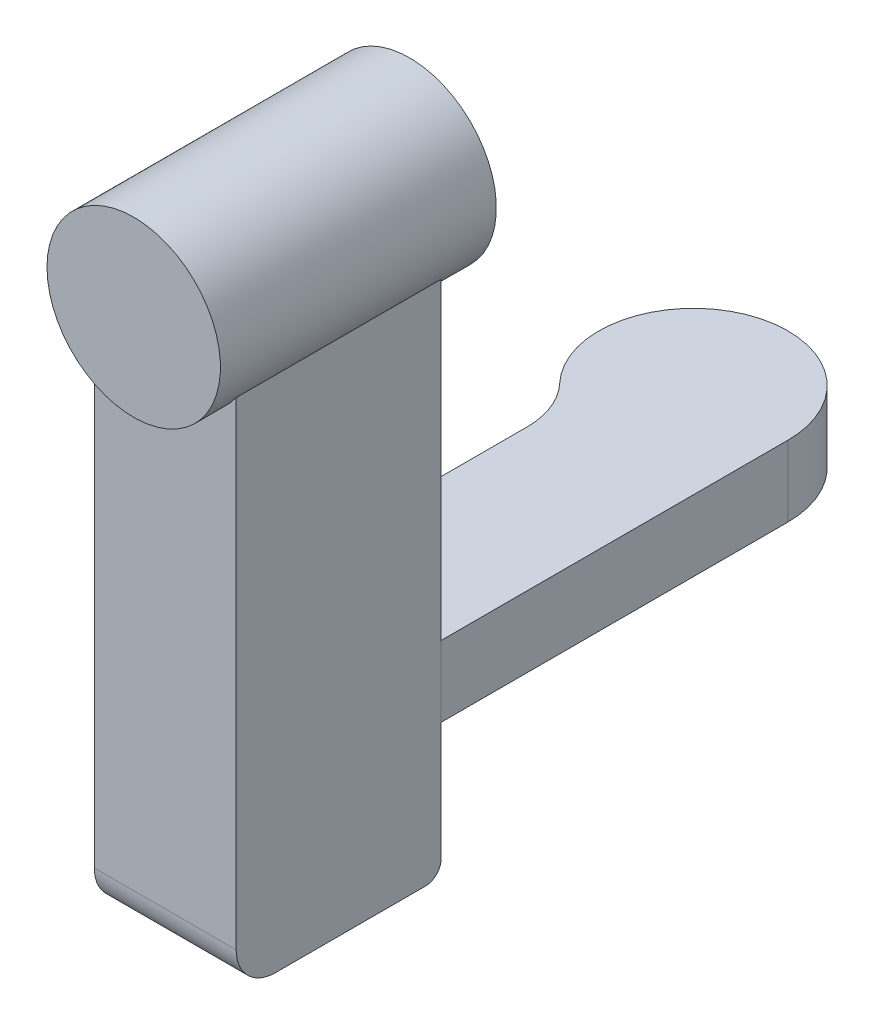
SolidWorks part; units mm, degrees
ref_plane "Front Plane" through (0, 0, 0) normal (0, 0, 1) x (1, 0, 0)
ref_plane "Top Plane" through (0, 0, 0) normal (0, 1, 0) x (1, 0, 0)
ref_plane "Right Plane" through (0, 0, 0) normal (1, 0, 0) x (0, 0, -1)
sketch "Sketch1" plane through (0, 0, 0) normal (0, 1, 0) x (1, 0, 0)
  line L0 (12, 0) -> (12, -44)
  line L1 (12, -44) -> (-6, -44)
  line L2 (-6, -44) -> (-6, -15.0997)
  arc A0 (12, 0) -> (-8.7273, -8.2362) centre (0, 0) ccw
  arc A1 (-6, -15.0997) -> (-8.7273, -8.2362) centre (-16, -15.0997) ccw
  dimension "D1" = 10
extrude "Boss-Extrude1" add sketch "Sketch1" along normal blind 9
ref_plane "Plane2" through (0, 9, 0) normal (0, 1, 0) x (1, 0, 0)
sketch "Sketch2" plane through (0, 9, 0) normal (0, 1, 0) x (1, 0, 0)
  line L1 (12, -44) -> (-6, -44)
  line L2 (12, -44) -> (12, -70)
  line L3 (12, -70) -> (-6, -70)
  line L4 (-6, -44) -> (-6, -70)
  dimension "D1" = 26
extrude "Boss-Extrude2" add sketch "Sketch2" along normal blind 40 and the other way blind 26 separate body
fillet "Fillet2" radius 2 1 edges at (3, -17, 44) type face fillet first side face at (3, 16, 44) second side face at (3, -17, 57)
fillet "Fillet3" radius 5 1 edges at (3, -17, 70) type face fillet first side face at (3, -17, 58) second side face at (3, 16, 70)
ref_plane "Plane3" through (0, 0, 44) normal (0, 0, -1) x (-1, 0, 0)
sketch "Sketch3" plane through (0, 0, 44) normal (0, 0, -1) x (-1, 0, 0)
  line L0 (-12, 49) -> (6, 49) construction
  circle A0 centre (-3, 55) radius 11
  dimension "D1" = 6
extrude "Boss-Extrude3" add sketch "Sketch3" along normal blind 5 and the other way blind 30
ref_point "Point1"
ref_point "Point2"
ref_axis "Axis1" through (0, 0, 0) along (0, 1, 0)
